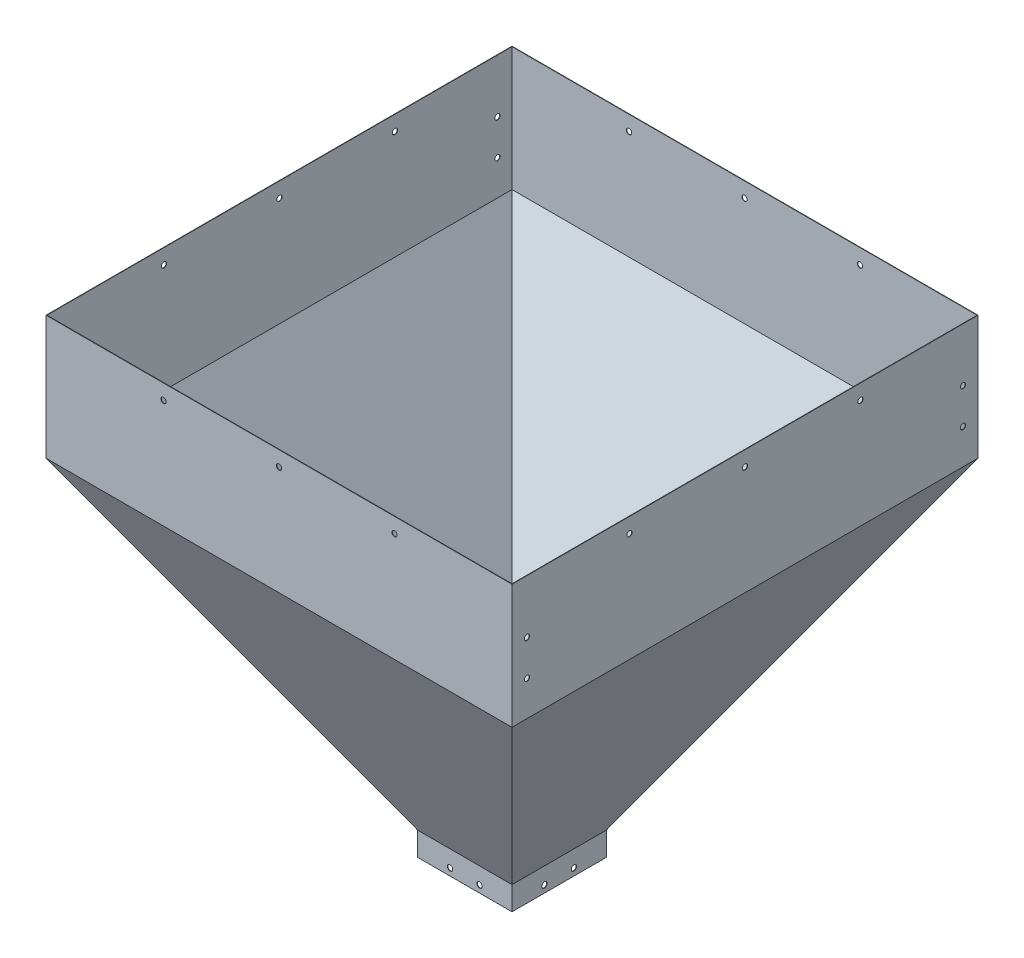
SolidWorks part; units mm, degrees
material "AISI 304"
ref_plane "Alzado" through (0, 0, 0) normal (0, 0, 1) x (1, 0, 0)
ref_plane "Planta" through (0, 0, 0) normal (0, 1, 0) x (1, 0, 0)
ref_plane "Vista lateral" through (0, 0, 0) normal (1, 0, 0) x (0, 0, -1)
sketch "Croquis1" plane through (0, 0, 0) normal (0, 1, 0) x (1, 0, 0)
  line L1 (-395, 395) -> (395, 395)
  line L2 (-395, 395) -> (-395, -395)
  line L3 (-395, -395) -> (395, -395)
  line L4 (395, 395) -> (395, -395)
  line L5 (-395, 395) -> (395, -395) construction
  line L6 (-395, -395) -> (395, 395) construction
  point P0 (0, 0)
  dimension "D1" = 790
ref_plane "Plano1" through (0, -546, 0) normal (0, 1, 0) x (1, 0, 0)
sketch "Croquis2" plane through (0, -546, 0) normal (0, 1, 0) x (1, 0, 0)
  line L0 (-395, 395) -> (395, -395) construction
  line L1 (-80, 80) -> (80, 80)
  line L2 (-80, 80) -> (-80, -80)
  line L3 (-80, -80) -> (80, -80)
  line L4 (80, 80) -> (80, -80)
  line L5 (-80, 80) -> (80, -80) construction
  line L6 (-80, -80) -> (80, 80) construction
  point P0 (0, 0)
  dimension "D1" = 160
loft "Recubrir1" add profiles "Croquis1", "Croquis2" connector at (-395, 0, -395) connector at (-80, -546, -80)
sketch "Croquis3" plane through (0, 0, 0) normal (0, 1, 0) x (1, 0, 0)
  line L1 (-395, 395) -> (395, 395)
  line L2 (-395, 395) -> (-395, -395)
  line L3 (-395, -395) -> (395, -395)
  line L4 (395, 395) -> (395, -395)
extrude "Saliente-Extruir1" add sketch "Croquis3" along normal blind 210
shell "Vaciado2" thickness 0.76 removed face at (0, -546, 0) removed face at (0, 210, 0)
sketch "Croquis5" plane through (0, -546, 0) normal (0, -1, 0) x (1, 0, 0)
  line L1 (-80, 80) -> (80, 80)
  line L2 (-80, 80) -> (-80, -80)
  line L3 (-80, -80) -> (80, -80)
  line L4 (80, 80) -> (80, -80)
  line L5 (-80, 80) -> (80, -80) construction
  line L6 (-80, -80) -> (80, 80) construction
  line L7 (79.1226, -79.1226) -> (-79.1226, -79.1226)
  line L8 (79.1226, -79.1226) -> (79.1226, 79.1226)
  line L9 (79.1226, 79.1226) -> (-79.1226, 79.1226)
  line L10 (-79.1226, -79.1226) -> (-79.1226, 79.1226)
  line L11 (79.1226, -79.1226) -> (-79.1226, 79.1226) construction
  line L12 (79.1226, 79.1226) -> (-79.1226, -79.1226) construction
  point P4 (0, 0)
  point P11 (0, 0)
extrude "Saliente-Extruir2" add sketch "Croquis5" along normal blind 40
hole_wizard "Taladro de margen para M81" positions "Croquis6" profile "Croquis7" hole size "M8" standard "Ansi Metric"
sketch "Croquis6" plane through (99.2416, -484.7014, -395) normal (0, 0, -1) x (-1, 0, 0)
  point P0 (99.2416, 669.2917)
  point P1 (-96.5584, 669.2917)
  point P2 (295.0416, 669.2917)
sketch "Croquis7" plane through (0, 184.5904, -395) normal (1, 0, 0) x (0, 1, 0)
  line L0 (0, 0) -> (0, 840.799)
  line L1 (0, 840.799) -> (4.5, 840.799)
  line L2 (4.5, 840.799) -> (4.5, 0)
  line L3 (4.5, 0) -> (0, 0)
  line L4 (0, -6.35) -> (0, 107.95) construction
  dimension "Diámetro de taladro hasta el siguiente" = 9
  dimension "Profundidad de taladro hasta el siguiente" = 840.799
hole_wizard "Taladro de margen para M82" positions "Croquis8" profile "Croquis9" hole size "M8" standard "Ansi Metric"
sketch "Croquis8" plane through (-395, -484.7014, -1480.0002) normal (-1, 0, 0) x (0, 0, 1)
  point P0 (1284.2002, 669.2917)
  point P1 (1480.0002, 669.2917)
  point P2 (1675.8002, 669.2917)
  point P3 (1849.6002, 603.8917)
  point P4 (1849.6002, 543.8917)
  point P5 (1110.4002, 543.8917)
  point P6 (1110.4002, 603.8917)
sketch "Croquis9" plane through (-395, 184.5904, -195.8) normal (0, 1, 0) x (0, 0, 1)
  line L0 (0, 0) -> (0, 840.799)
  line L1 (0, 840.799) -> (4.5, 840.799)
  line L2 (4.5, 840.799) -> (4.5, 0)
  line L3 (4.5, 0) -> (0, 0)
  line L4 (0, -6.35) -> (0, 107.95) construction
  dimension "Diámetro de taladro hasta el siguiente" = 9
  dimension "Profundidad de taladro hasta el siguiente" = 840.799
hole_wizard "Taladro de margen para M85" positions "Croquis10" profile "Croquis11" hole size "M8" standard "Ansi Metric" end condition through all
sketch "Croquis10" plane through (99.2416, -484.7014, 80) normal (0, 0, 1) x (1, 0, 0)
  point P0 (-124.2416, -89.2986)
  point P1 (-74.2416, -89.2986)
sketch "Croquis11" plane through (-25, -574, 80) normal (1, 0, 0) x (0, -1, 0)
  line L0 (0, 0) -> (0, 475.0001)
  line L1 (0, 475.0001) -> (4.5, 475.0001)
  line L2 (4.5, 475.0001) -> (4.5, 0)
  line L5 (4.5, 0) -> (0, 0)
  line L11 (0, -6.35) -> (0, 107.95) construction
  dimension "Diámetro de taladro hasta el siguiente" = 9
  dimension "Profundidad de taladro hasta el siguiente" = 475.0001
hole_wizard "Taladro de margen para M86" positions "Croquis12" profile "Croquis13" hole size "M8" standard "Ansi Metric" end condition through all
sketch "Croquis12" plane through (-80, -484.7014, -1480.0002) normal (-1, 0, 0) x (0, 0, 1)
  point P0 (1505.0002, -89.2986)
  point P1 (1455.0002, -89.2986)
sketch "Croquis13" plane through (-80, -574, 25) normal (0, 1, 0) x (0, 0, 1)
  line L0 (0, 0) -> (0, 475.0001)
  line L1 (0, 475.0001) -> (4.5, 475.0001)
  line L2 (4.5, 475.0001) -> (4.5, 0)
  line L5 (4.5, 0) -> (0, 0)
  line L11 (0, -6.35) -> (0, 107.95) construction
  dimension "Diámetro de taladro hasta el siguiente" = 9
  dimension "Profundidad de taladro hasta el siguiente" = 475.0001
